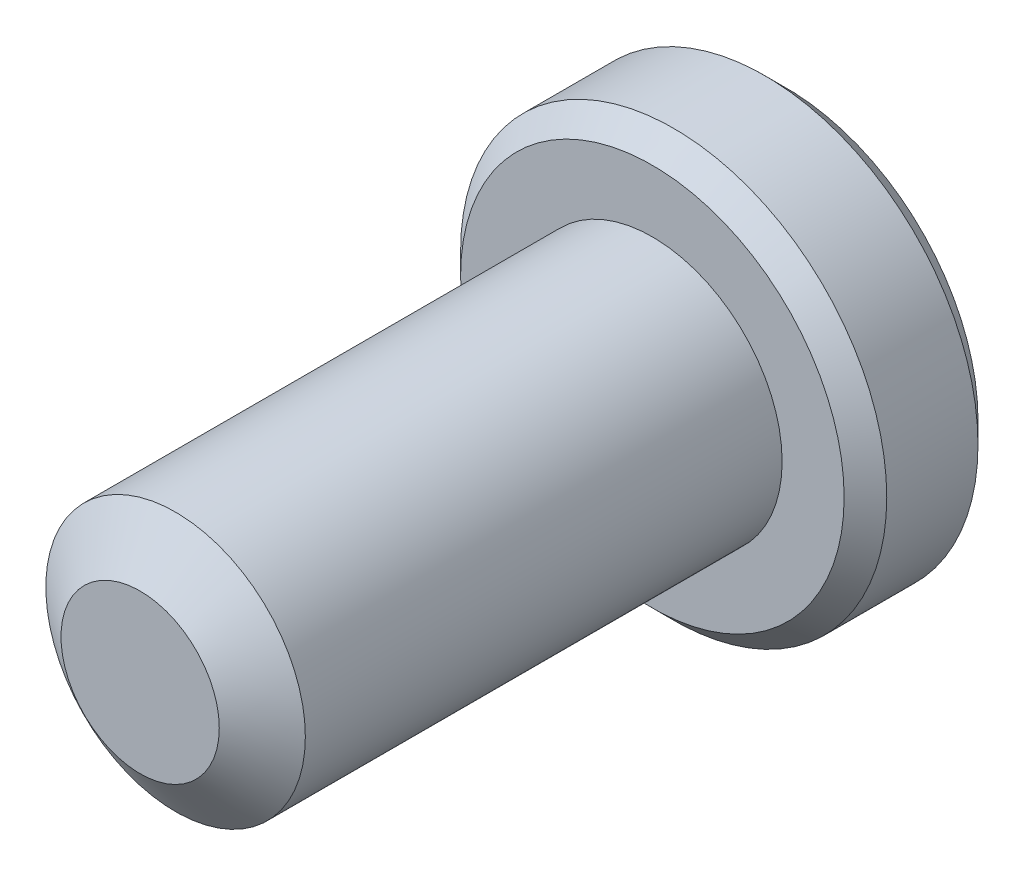
SolidWorks part; units mm, degrees
ref_plane "Front Plane" through (0, 0, 0) normal (0, 0, 1) x (1, 0, 0)
ref_plane "Top Plane" through (0, 0, 0) normal (0, 1, 0) x (1, 0, 0)
ref_plane "Right Plane" through (0, 0, 0) normal (1, 0, 0) x (0, 0, -1)
sketch "Sketch1" plane through (0, 0, 0) normal (0, 0, 1) x (1, 0, 0)
  circle A0 centre (0, 0) radius 2.413
  dimension "OD" = 4.826
extrude "Extrude1" add sketch "Sketch1" against normal blind 9.525
sketch "Sketch2" plane through (0, 0, 0) normal (0, 0, 1) x (1, 0, 0)
  circle A0 centre (0, 0) radius 2.413 construction
  circle A1 centre (0, 0) radius 2.413
curve "Helix/Spiral1" [suppressed] pitch 1.0583 height 10.5833 turns 10 parameters "pitch"=1.0583
sketch "Sketch3" plane through (0, 0, 0) normal (1, 0, 0) x (0, 0, -1)
  line L0 (-0.926, 2.413) -> (-0.5292, 1.7256)
  line L1 (-0.5292, 1.7256) -> (-0.3969, 1.7256)
  line L2 (-0.3969, 1.7256) -> (0, 2.413)
  line L3 (-0.926, 2.413) -> (0, 2.413)
  line L4 (-0.463, 2.413) -> (-0.463, 1.7256) construction
  line L5 (-0.7276, 2.0693) -> (-0.1984, 2.0693) construction
  line L6 (0, 2.413) -> (0, -2.413) construction
  dimension "D1" = 0.1323
  dimension "D2" = 0.5292
  dimension "D3" = 60
sweep "Cut-Sweep1" [suppressed] cut profiles "Sketch3" path "Helix/Spiral1"
sketch "Sketch4" plane through (0, 0, 0) normal (1, 0, 0) x (0, 0, -1)
  line L0 (0.6592, 2.413) -> (0, 1.4716)
  line L1 (0, 1.4716) -> (0, 2.413)
  line L2 (0.6592, 2.413) -> (0, 2.413)
  line L3 (-0.926, 2.413) -> (0, 2.413) construction
  line L4 (0, 0) -> (7.0209, 0) construction
  dimension "D1" = 55
  dimension "D2" = 0.254
revolve "Cut-Revolve1" cut sketch "Sketch4" angle 360 about L4
sketch "Sketch6" plane through (0, 0, -9.525) normal (0, 0, -1) x (-1, 0, 0)
  circle A0 centre (0, 0) radius 3.9624
  dimension "head dia" = 7.9248
extrude "Extrude2" add sketch "Sketch6" along normal blind 2.4892
sketch "Sketch7" plane through (0, 0, -12.0142) normal (0, 0, -1) x (-1, 0, 0)
  line L1 (0, 1.3748) -> (-1.1906, 0.6874)
  line L2 (-1.1906, 0.6874) -> (-1.1906, -0.6874)
  line L3 (-1.1906, -0.6874) -> (0, -1.3748)
  line L4 (0, -1.3748) -> (1.1906, -0.6874)
  line L5 (1.1906, -0.6874) -> (1.1906, 0.6874)
  line L6 (1.1906, 0.6874) -> (0, 1.3748)
  circle A0 centre (0, 0) radius 1.1906 construction
  dimension "hex dia" = 2.3813
extrude "Cut-Extrude1" cut sketch "Sketch7" against normal blind 1.7859
sketch "Sketch8" plane through (0, 0, -12.0142) normal (0, 0, -1) x (-1, 0, 0)
  circle A0 centre (0, 0) radius 1.3748
extrude "Cut-Extrude2" cut sketch "Sketch8" against normal through all draft 45
chamfer "Chamfer1" distance 0.3962 angle 45 2 edges at (-3.9624, 0, -12.0142) (-3.9624, 0, -9.525)
sketch "Sketch10" plane through (0, 0, -9.525) normal (0, 0, 1) x (1, 0, 0)
  circle A1 centre (0, 0) radius 2.413
  circle A2 centre (0, 0) radius 2.413
  dimension "D1" = 0
ref_plane "Plane1" through (0, 0, 0) normal (0, 0, 1) x (1, 0, 0)
extrude "partial thread" [suppressed] add sketch "Sketch10" along normal up to surface (12.7 mm away) separate body up to plane "Plane1"
chamfer "Chamfer2" [suppressed] distance 0.0965 angle 45
combine bodies "Combine1" [suppressed] operation type add bodies to combine 107 108
sketch "Sketch9" plane through (0, 0, 0) normal (1, 0, 0) x (0, 0, -1)
  line L0 (0, 2.413) -> (0, -2.413) construction
  line L1 (2.6458, 2.413) -> (2.6458, -2.413) construction
  dimension "D1" = 2.6458
sketch "Sketch11" plane through (0, 0, -9.525) normal (0, 0, 1) x (1, 0, 0)
  circle A0 centre (0, 0) radius 3.175
  dimension "Shoulder Diameter" = 6.35
equation "\"D3@Helix/Spiral1\" = \"screw length@Extrude1\"+\"pitch@Helix/Spiral1\""
equation "\"D1@Sketch3\" = \"pitch@Helix/Spiral1\"*.125"
equation "\"D2@Sketch3\" = \"pitch@Helix/Spiral1\"*.5"
equation "\"D1@Cut-Extrude1\" = \"hex dia@Sketch7\"*.75"
equation "\"D1@Chamfer1\" = \"head dia@Sketch6\"*.05"
equation "\"D1@Sketch9\" = \"pitch@Helix/Spiral1\"*2.5"
equation "\"D1@Chamfer2\"=\"OD@Sketch1\"*.02"
